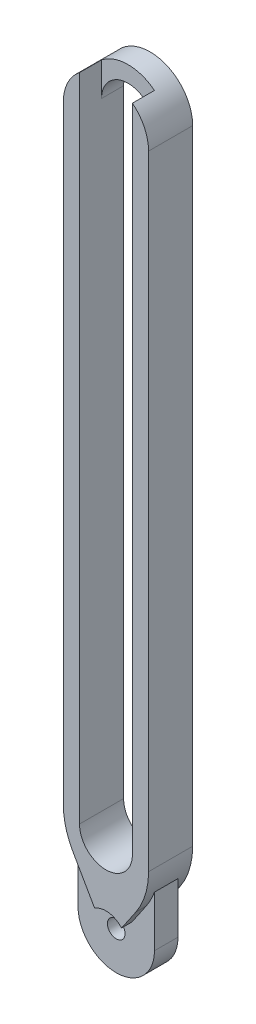
SolidWorks part; units mm, degrees
material "PET"
ref_plane "Piano frontale" through (0, 0, 0) normal (0, 0, 1) x (1, 0, 0)
ref_plane "Piano superiore" through (0, 0, 0) normal (0, 1, 0) x (1, 0, 0)
ref_plane "Piano destro" through (0, 0, 0) normal (1, 0, 0) x (0, 0, -1)
sketch "Schizzo1" plane through (0, 0, 0) normal (0, 0, 1) x (1, 0, 0)
  line L0 (0, 182.0114) -> (0, -37.9886) construction
  line L1 (14.5, 182.0114) -> (14.5, -37.9886)
  line L2 (-14.5, 182.0114) -> (-14.5, -37.9886)
  arc A0 (14.5, 182.0114) -> (-14.5, 182.0114) centre (0, 182.0114) ccw
  arc A1 (-14.5, -37.9886) -> (14.5, -37.9886) centre (0, -37.9886) ccw
  point P3 (0, 72.0114)
  dimension "D1" = 29
  dimension "D2" = 220
extrude "Estrusione-Estrusione1" add sketch "Schizzo1" along normal mid plane 15
sketch "Schizzo3" plane through (0, 0, 0) normal (0, 0, 1) x (1, 0, 0)
  line L0 (-14.5, -37.9886) -> (14.5, -37.9886) construction
sketch "Schizzo2" plane through (0, 0, 0) normal (0, 0, 1) x (1, 0, 0)
  line L0 (0, -40.0666) -> (0, -56.0666) construction
  line L1 (13, -40.0666) -> (13, -56.0666)
  line L2 (-13, -40.0666) -> (-13, -56.0666)
  line L3 (-14.5, -37.9886) -> (14.5, -37.9886) construction
  arc A0 (13, -40.0666) -> (-13, -40.0666) centre (0, -40.0666) ccw
  arc A1 (-13, -56.0666) -> (13, -56.0666) centre (0, -56.0666) ccw
  point P3 (0, -48.0666)
  dimension "D1" = 16
  dimension "D2" = 13
  dimension "D3" = 2.078
extrude "Estrusione-Estrusione2" add sketch "Schizzo2" along normal mid plane 8
sketch "Schizzo4" plane through (0, 0, 4) normal (0, 0, 1) x (1, 0, 0)
  line L0 (13, -56.0666) -> (0, -56.0666) construction
  line L1 (5.2945, -51.4875) -> (14.5, -37.9886)
  line L2 (14.5, -37.9886) -> (21.4943, -44.738)
  line L3 (-3.8458, -50.2177) -> (-14.5, -31.5622)
  line L4 (-14.5, -31.5622) -> (-28.5961, -39.4536)
  line L5 (-28.5961, -39.4536) -> (-5.2945, -60.6458)
  line L6 (-14.5, 182.0114) -> (-14.5, -37.9886) construction
  line L7 (21.4943, -44.738) -> (5.3865, -60.5371)
  arc A0 (-5.2945, -60.6458) -> (5.3865, -60.5371) centre (0, -56.0666) ccw
  arc A1 (-13, -44.4112) -> (13, -44.4112) centre (0, -37.9886) ccw construction
  arc A3 (5.2945, -51.4875) -> (-3.8458, -50.2177) centre (0, -56.0666) ccw
  dimension "D1" = 14
extrude "Taglio-Estrusione1" cut sketch "Schizzo4" along normal through all
mirror "Specchia1" about plane through (0, 0, 0) normal (0, 0, 1) of "Taglio-Estrusione1"
sketch "Schizzo5" plane through (0, 0, 4) normal (0, 0, 1) x (1, 0, 0)
  line L0 (-13, -44.4112) -> (-13, -34.1887)
  line L1 (-3.8458, -50.2177) -> (-14.5, -31.5622) construction
  line L2 (-13, -34.1887) -> (-15.0563, -30.5881)
  line L3 (-15.0563, -30.5881) -> (-15.0563, -43.6194)
  line L4 (-15.0563, -43.6194) -> (-13, -44.4112)
  line L5 (13, -44.4112) -> (13, -40.1882)
  line L6 (14.5, -37.9886) -> (5.2945, -51.4875) construction
  line L7 (13, -40.1882) -> (17.408, -33.7244)
  line L8 (17.408, -33.7244) -> (17.408, -44.4112)
  line L9 (17.408, -44.4112) -> (13, -44.4112)
extrude "Taglio-Estrusione2" cut sketch "Schizzo5" against normal through all
fillet "Raccordo1" radius 25 2 edges at (-14.5, -31.5622, 0) (14.5, -37.9886, 0)
sketch "Schizzo6" plane through (0, 0, 4) normal (0, 0, 1) x (1, 0, 0)
  line L0 (13, -56.0666) -> (0, -56.0666) construction
  circle A0 centre (0, -56.0666) radius 3
sketch "Schizzo8" plane through (0, 0, 0) normal (0, 0, 1) x (1, 0, 0)
  line L0 (0, 182.0114) -> (0, -27.9886) construction
  line L1 (9, 182.0114) -> (9, -27.9886)
  line L2 (-9, 182.0114) -> (-9, -27.9886)
  arc A0 (9, 182.0114) -> (-9, 182.0114) centre (0, 182.0114) ccw
  arc A1 (-9, -27.9886) -> (9, -27.9886) centre (0, -27.9886) ccw
  point P4 (0, 77.0114)
  dimension "D1" = 18
  dimension "D2" = 210
extrude "Taglio-Estrusione3" cut sketch "Schizzo8" against normal mid plane 15
sketch "Schizzo9" plane through (0, 0, 7.5) normal (0, 0, 1) x (1, 0, 0)
  line L0 (0, 182.0114) -> (0, 202.0114) construction
  line L1 (-9, 182.0114) -> (-9, 202.0114)
  line L2 (9, 182.0114) -> (9, 202.0114)
  arc A0 (-9, 182.0114) -> (9, 182.0114) centre (0, 182.0114) ccw
  arc A1 (9, 202.0114) -> (-9, 202.0114) centre (0, 202.0114) ccw
  point P4 (0, 192.0114)
  dimension "D1" = 18
  dimension "D2" = 20
extrude "Taglio-Estrusione4" cut sketch "Schizzo9" against normal blind 7.5
sketch "Schizzo10" plane through (9, 0, 0) normal (-1, 0, 0) x (0, 0, 1)
  line L0 (-7.5, 77.0114) -> (7.5, 77.0114) construction
  line L1 (-7.5, -27.9886) -> (-7.5, 182.0114) construction
  line L2 (7.5, -27.9886) -> (7.5, 193.3802) construction
sketch "Schizzo12" plane through (0, 0, -7.5) normal (0, 0, -1) x (-1, 0, 0)
  line L0 (-9.0669, 77.0114) -> (9, 77.0114) construction
  line L1 (9, 182.0114) -> (9, -27.9886) construction
extrude "Taglio-Estrusione5" cut sketch "Schizzo6" against normal through all
